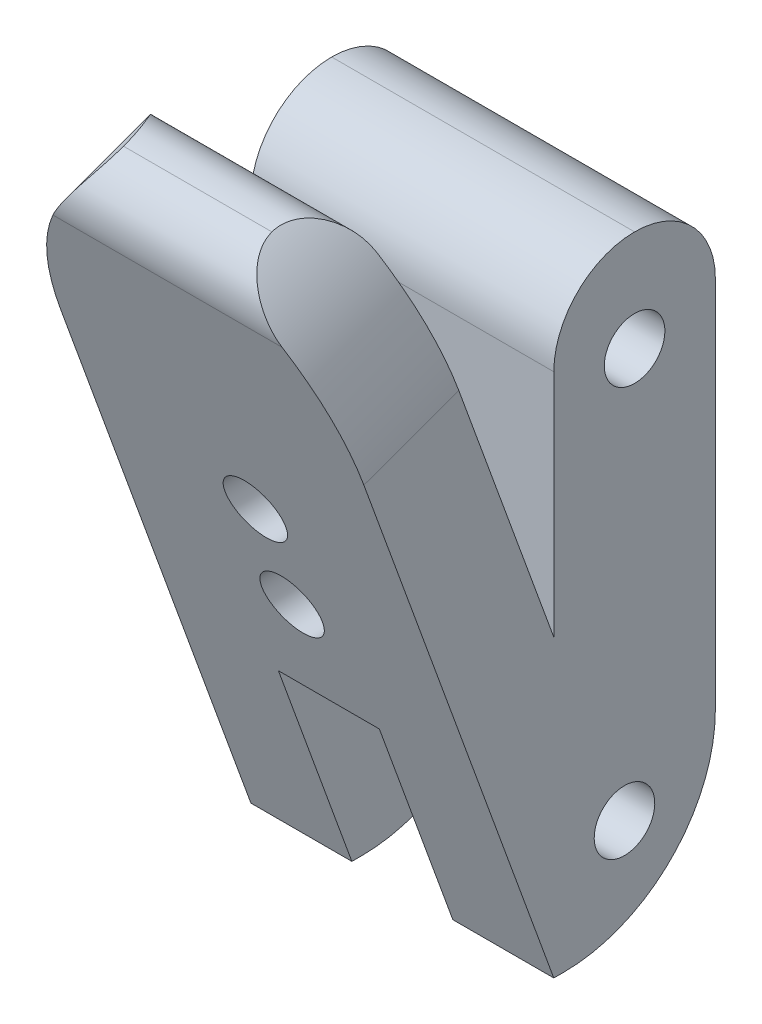
SolidWorks part; units mm, degrees
ref_plane "Front Plane" through (0, 0, 0) normal (0, 0, 1) x (1, 0, 0)
ref_plane "Top Plane" through (0, 0, 0) normal (0, 1, 0) x (1, 0, 0)
ref_plane "Right Plane" through (0, 0, 0) normal (1, 0, 0) x (0, 0, -1)
sketch "Sketch1" plane through (0, 0, 0) normal (0, 0, 1) x (1, 0, 0)
  line L0 (0, 0) -> (30, 0)
  line L1 (30, 0) -> (30, -60)
  line L2 (30, -60) -> (0, -60)
  line L3 (0, -60) -> (0, 0)
extrude "Boss-Extrude1" add sketch "Sketch1" along normal blind 15 and the other way blind 1
sketch "Sketch2" plane through (0, 0, 0) normal (-1, 0, 0) x (0, 0, 1)
  circle A0 centre (7, -10) radius 3
  point P4 (7, -9.5841)
extrude "Cut-Extrude1" cut sketch "Sketch2" against normal blind 49
fillet "Fillet1" radius 8 2 edges at (15, 0, 15) (15, 0, -1)
ref_plane "Plane1" through (0, -11.8396, 32.529) normal (0, 0.342, -0.9397) x (1, 0, 0)
sketch "Sketch6" plane through (0, -11.8396, 32.529) normal (0, 0.342, -0.9397) x (1, 0, 0)
  line L0 (30, 51.2513) -> (0, 51.2513)
  line L1 (0, 51.2513) -> (0, -28.7487)
  line L2 (0, 2.3872) -> (0, 51.2513) construction
  line L3 (0, -28.7487) -> (30, -28.7487)
  line L4 (30, 51.2513) -> (30, -28.7487)
extrude "Boss-Extrude2" add sketch "Sketch6" along normal blind 10
sketch "Sketch7" plane through (0, 0, -1) normal (0, 0, -1) x (-1, 0, 0)
  circle A2 centre (-15, -20) radius 3
  circle A3 centre (-15, -30) radius 3
  point P0 (0, 0)
extrude "Cut-Extrude2" cut sketch "Sketch7" against normal blind 38
sketch "Sketch8" plane through (0, 0, 0) normal (-1, 0, 0) x (0, 0, 1)
  circle A0 centre (8, -50) radius 3
extrude "Cut-Extrude3" cut sketch "Sketch8" against normal blind 49
sketch "Sketch11" plane through (0, 0, -1) normal (0, 0, -1) x (-1, 0, 0)
  line L2 (0, -60) -> (-30, -60) construction
  line L4 (-20, -60) -> (-10, -60)
  line L13 (-20, -40) -> (-20, -60)
  line L14 (-20, -40) -> (-10, -40)
  line L15 (-10, -40) -> (-10, -60)
extrude "Cut-Extrude4" cut sketch "Sketch11" against normal blind 30
fillet "Fillet2" radius 15 2 edges at (5, -60, -1) (25, -60, -1)
fillet "Fillet3" radius 25 2 edges at (0, 16.8855, 37.6631) (30, 16.8855, 37.6631)
sketch "Sketch12" plane through (0, -8.4194, 23.132) normal (0, 0.342, -0.9397) x (-1, 0, 0)
  line L1 (-15, 21.7484) -> (-7.6503, 21.7484)
  line L2 (-15, 21.7484) -> (-22.3497, 21.7484)
  arc A0 (0, 3.7487) -> (-15, 26.6616) centre (-25, 3.7487) ccw construction
  arc A1 (-15, 26.6616) -> (-30, 3.7487) centre (-5, 3.7487) ccw construction
  arc A2 (-22.3497, 21.7484) -> (-7.6503, 21.7484) centre (-15, 19.3615) cw
extrude "Cut-Extrude5" cut sketch "Sketch12" against normal blind 10
fillet "Fillet5" radius 5 2 edges at (15, 8.5972, 39.9673) (15, 12.0174, 30.5704)
